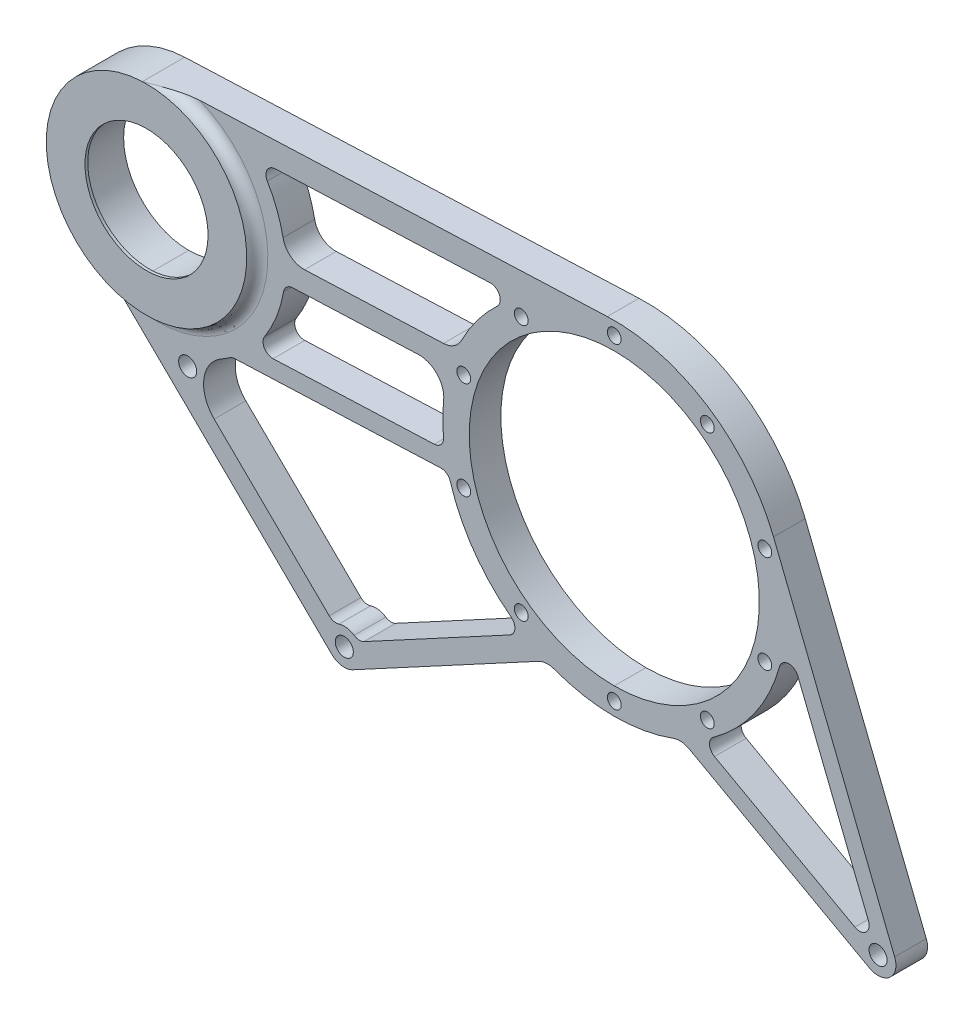
SolidWorks part; units mm, degrees
material "6061-T6 (SS)"
ref_plane "Front Plane" through (0, 0, 0) normal (0, 0, 1) x (1, 0, 0)
ref_plane "Top Plane" through (0, 0, 0) normal (0, 1, 0) x (1, 0, 0)
ref_plane "Right Plane" through (0, 0, 0) normal (1, 0, 0) x (0, 0, -1)
sketch "Sketch1" plane through (0, 0, 0) normal (0, 0, 1) x (1, 0, 0)
  line L0 (-114.3, 95.25) -> (-114.3, 107.95) construction
  line L1 (-280.8642, 163.1704) -> (-116.8043, 169.8118)
  line L2 (-304.7421, 101.1501) -> (-216.3071, 14.4521)
  line L3 (-13.0706, 21.4387) -> (-56.8054, 130.918)
  line L4 (-208.742, 13.3833) -> (-141.7118, 49.5504)
  line L5 (-22.1639, 13.4141) -> (-87.2342, 49.3665)
  circle A0 centre (-279.4, 127) radius 23.5
  circle A1 centre (-114.3, 95.25) radius 36 construction
  circle A2 centre (0, 0) radius 12.7 construction
  circle A3 centre (-228.6, 0) radius 12.7 construction
  circle A4 centre (-114.3, 107.95) radius 52.3875
  circle A5 centre (-19.05, 19.05) radius 3.2639
  circle A6 centre (-211.7995, 19.05) radius 3.2639
  circle A7 centre (-279.4, 127) radius 36.2
  arc A8 (-135.9521, 49.947) -> (-93.0137, 49.8118) centre (-114.3, 107.95) ccw
  arc A9 (-216.3071, 14.4521) -> (-208.742, 13.3833) centre (-211.7995, 19.05) ccw
  arc A10 (-22.1639, 13.4141) -> (-13.0706, 21.4387) centre (-19.05, 19.05) ccw
  arc A11 (-56.8054, 130.918) -> (-116.8043, 169.8118) centre (-114.3, 107.95) ccw
  arc A12 (-135.9521, 49.947) -> (-141.7118, 49.5504) centre (-138.3949, 43.4031) ccw
  arc A13 (-87.2342, 49.3665) -> (-93.0137, 49.8118) centre (-90.6122, 43.2526) ccw
  dimension "D5" = 72
  dimension "D6" = 47
  dimension "D7" = 25.4
  dimension "D8" = 25.4
  dimension "D11" = 104.775
  dimension "D14" = 6.5278
  dimension "D15" = 6.5278
  dimension "D16" = 25.4
  dimension "D17" = 12.7
  dimension "D18" = 123.825
  dimension "D19" = 3.175
  dimension "D20" = 6.985
  dimension "D21" = 6.985
  dimension "D1" = 114.3
  dimension "D2" = 95.25
  dimension "D3" = 279.4
  dimension "D4" = 127
  dimension "D9" = 228.6
  dimension "D10" = 12.7
  dimension "D12" = 19.05
  dimension "D13" = 19.05
extrude "Boss-Extrude1" add sketch "Sketch1" along normal blind 11.43 contours A13 L5 A10 L3 A11 L1 A7 L2 A9 L4 A12 A8 A6 A5 A4 | A7 A0 region at (-168.693, 91.0379, 0) region at (-255.035, 152.3713, 0)
sketch "Sketch2" plane through (0, 0, 11.43) normal (0, 0, 1) x (1, 0, 0)
  circle A0 centre (-279.4, 127) radius 36.2
  circle A1 centre (-279.4, 127) radius 23.5
extrude "Boss-Extrude2" add sketch "Sketch2" along normal blind 3.81
fillet "Fillet1" radius 3.81 1 edges at (-245.6173, 113.9936, 11.43)
sketch "Sketch3" plane through (0, 0, 11.43) normal (0, 0, 1) x (1, 0, 0)
  line L0 (-114.3, 107.95) -> (-114.3, 165.1) construction
  circle A0 centre (-114.3, 107.95) radius 57.15 construction
  circle A1 centre (-114.3, 165.1) radius 2.5
  circle A2 centre (-80.7081, 154.1853) radius 2.5
  circle A3 centre (-59.9471, 125.6103) radius 2.5
  circle A4 centre (-59.9471, 90.2897) radius 2.5
  circle A5 centre (-80.7081, 61.7147) radius 2.5
  circle A6 centre (-114.3, 50.8) radius 2.5
  circle A7 centre (-147.8919, 61.7147) radius 2.5
  circle A8 centre (-168.6529, 90.2897) radius 2.5
  circle A9 centre (-168.6529, 125.6103) radius 2.5
  circle A10 centre (-147.8919, 154.1853) radius 2.5
  point P25 (-114.3, 107.95)
  dimension "D1" = 114.3
  dimension "D2" = 5
  dimension "D3" = 10
extrude "5mm Holes" cut sketch "Sketch3" against normal through all
sketch "Sketch4" plane through (0, 0, 15.24) normal (0, 0, 1) x (1, 0, 0)
  circle A0 centre (-279.4, 127) radius 22.225
  circle A1 centre (-279.4, 127) radius 23.5 construction
  circle A2 centre (-279.4, 127) radius 23.5
  dimension "D1" = 44.45
extrude "Boss-Extrude3" add sketch "Sketch4" against normal blind 1
sketch "Sketch5" plane through (0, 0, 11.43) normal (0, 0, 1) x (1, 0, 0)
  line L0 (-48.0193, 91.8071) -> (-22.5033, 27.9342)
  line L1 (-13.0706, 21.4387) -> (-56.8054, 130.918) construction
  line L2 (-78.1047, 51.5771) -> (-27.4356, 23.5816)
  line L3 (-22.1639, 13.4141) -> (-87.2342, 49.3665) construction
  line L4 (-236.7455, 156.0591) -> (-159.125, 159.2013)
  line L5 (-263.8382, 163.8596) -> (-116.8043, 169.8118) construction
  line L6 (-226.1253, 129.7972) -> (-175.9845, 131.827)
  line L7 (-230.4174, 121.9972) -> (-185.1154, 123.8311)
  line L8 (-258.7869, 66.7686) -> (-217.2302, 26.028)
  line L9 (-204.6483, 24.2506) -> (-152.0143, 52.6499)
  line L10 (-292.5742, 89.2212) -> (-216.3071, 14.4521) construction
  line L11 (-208.742, 13.3833) -> (-141.7118, 49.5504) construction
  line L12 (-237.4937, 96.2899) -> (-179.3047, 98.6455)
  line L13 (-251.3498, 89.3738) -> (-177.0086, 92.3833)
  arc A0 (-175.0426, 119.9291) -> (-175.9673, 102.4457) centre (-114.3, 107.95) ccw construction
  circle A1 centre (-211.7995, 19.05) radius 6.4389 construction
  circle A2 centre (-19.05, 19.05) radius 6.4389 construction
  arc A3 (-54.6287, 91.4427) -> (-78.4387, 57.481) centre (-114.3, 107.95) cw
  arc A4 (-48.0193, 91.8071) -> (-54.6287, 91.4427) centre (-51.2626, 90.5115) ccw
  arc A5 (-27.4356, 23.5816) -> (-22.5033, 27.9342) centre (-25.7466, 26.6385) ccw
  arc A6 (-78.1047, 51.5771) -> (-78.4387, 57.481) centre (-76.4157, 54.634) cw
  arc A7 (-233.9104, 135.9413) -> (-239.6024, 150.7781) centre (-279.4, 127) ccw construction
  arc A8 (-292.5742, 89.2212) -> (-263.8382, 163.8596) centre (-279.4, 127) ccw construction
  arc A9 (-213.7352, 25.191) -> (-208.2383, 24.4145) centre (-211.7995, 19.05) cw
  arc A10 (-156.5977, 153.1613) -> (-169.499, 135.9897) centre (-114.3, 107.95) ccw
  arc A11 (-175.9093, 114.0697) -> (-175.9673, 102.4457) centre (-114.3, 107.95) ccw
  arc A12 (-173.5263, 89.9112) -> (-151.5703, 58.5123) centre (-114.3, 107.95) ccw
  arc A13 (-239.6024, 150.7781) -> (-233.9104, 135.9413) centre (-279.4, 127) cw
  arc A14 (-233.7176, 119.1025) -> (-240.5609, 101.6865) centre (-279.4, 127) cw
  arc A15 (-240.5609, 101.6865) -> (-233.7176, 119.1025) centre (-279.4, 127) ccw construction
  arc A16 (-253.1835, 88.7646) -> (-256.2406, 86.8392) centre (-279.4, 127) cw
  arc A17 (-159.125, 159.2013) -> (-156.5977, 153.1613) centre (-158.9837, 155.7117) cw
  arc A20 (-236.7455, 156.0591) -> (-239.6024, 150.7781) centre (-236.6043, 152.5695) ccw
  arc A21 (-179.3047, 98.6455) -> (-175.9673, 102.4457) centre (-179.446, 102.1352) ccw
  arc A23 (-230.4174, 121.9972) -> (-233.7176, 119.1025) centre (-230.2762, 118.5075) ccw
  arc A24 (-237.4937, 96.2899) -> (-240.5609, 101.6865) centre (-237.6349, 99.7796) cw
  arc A25 (-217.2302, 26.028) -> (-213.7352, 25.191) centre (-214.7852, 28.522) ccw
  arc A26 (-204.6483, 24.2506) -> (-208.2383, 24.4145) centre (-206.3067, 27.3242) cw
  arc A27 (-152.0143, 52.6499) -> (-151.5703, 58.5123) centre (-153.6727, 55.7236) ccw
  arc A28 (-177.0086, 92.3833) -> (-173.5263, 89.9112) centre (-176.8673, 88.8936) cw
  arc A29 (-251.3498, 89.3738) -> (-253.1835, 88.7646) centre (-251.2085, 85.8842) ccw
  arc A31 (-173.5263, 89.9112) -> (-170.4887, 133.9499) centre (-114.3, 107.95) ccw construction
  arc A32 (-273.3418, 81.0375) -> (-253.1835, 88.7646) centre (-279.4, 127) ccw construction
  arc A33 (-258.7869, 66.7686) -> (-256.2406, 86.8392) centre (-249.8962, 75.8374) cw
  arc A34 (-169.499, 135.9897) -> (-175.9845, 131.827) centre (-176.2928, 139.4407) cw
  arc A35 (-233.9104, 135.9413) -> (-226.1253, 129.7972) centre (-226.4335, 137.411) ccw
  arc A36 (-185.1154, 123.8311) -> (-175.9093, 114.0697) centre (-184.7558, 114.9484) cw
  point P17 (-52.5701, 103.1988)
  point P23 (-83.2204, 54.4036)
  point P51 (-148.3837, 159.6362)
  point P54 (-171.3442, 132.0148)
  point P60 (-243.0732, 155.8029)
  point P63 (-175.5324, 98.7982)
  point P66 (-174.02, 124.2803)
  point P75 (-215.4925, 24.3245)
  point P78 (-206.7898, 23.0951)
  point P81 (-146.981, 55.3657)
  point P84 (-174.2524, 92.4948)
  point P90 (-273.3418, 81.0375)
  dimension "D1" = 123.825
  dimension "D2" = 12.8778
  dimension "D5" = 3.4925
  dimension "D6" = 6.35
  dimension "D14" = 3.4925
  dimension "D15" = 12.7
  dimension "D16" = 7.62
  dimension "D17" = 7.62
  dimension "D18" = 8.89
  dimension "D3" = 6.35
  dimension "D4" = 6.35
  dimension "D7" = 8.89
  dimension "D8" = 7.62
  dimension "D9" = 7.62
  dimension "D10" = 7.62
  dimension "D11" = 6.35
  dimension "D12" = 25.4
  dimension "D13" = 26.67
extrude "Cut-Extrude2" cut sketch "Sketch5" against normal through all both and the other way through all
ref_axis "Axis2" through (-279.4, 127, 14.24) along (0, 0, -1)
ref_axis "Axis1" through (-114.3, 107.95, 11.43) along (0, 0, -1)
ref_plane "Plane1" through (-114.3, 0, 0) normal (1, 0, 0) x (0, 0, -1)
ref_plane "Plane2" through (-279.4, 0, 0) normal (1, 0, 0) x (0, 0, -1)
ref_plane "Plane3" through (0, 0, 5.715) normal (0, 0, -1) x (-1, 0, 0)
ref_plane "Plane4" through (0, 0, 7.12) normal (0, 0, -1) x (-1, 0, 0)
split line "Split Line1"
split line "Split Line2"
sketch "Sketch6" plane through (0, 0, 5.715) normal (0, 0, -1) x (-1, 0, 0)
  circle A1 centre (114.3, 107.95) radius 52.3875 construction
sketch "Sketch7" plane through (0, 0, 7.12) normal (0, 0, -1) x (-1, 0, 0)
  circle A0 centre (279.4, 127) radius 23.5
sketch "Sketch8" plane through (0, 0, 11.43) normal (0, 0, 1) x (1, 0, 0)
  circle A0 centre (-268.3542, 78.4783) radius 3.2639
extrude "Cut-Extrude3" cut sketch "Sketch8" against normal through all both and the other way through all
ref_point "Puck Center"
ref_point "Bearing Center"
sketch "Sketch9" plane through (0, 0, 0) normal (0, 0, 1) x (1, 0, 0)
  point P0 (-48.5383, 56.2255)
  point P1 (-206.2691, 109.9745)
  point P2 (-217.3203, 145.1375)
  point P3 (-185.1714, 145.1375)
  point P4 (-230.3808, 72.3)
  point P5 (-206.2691, 46.179)
  point P6 (-185.1714, 69.286)
  point P7 (-113.8939, 82.1055)
  point P8 (-149.5374, 107.95)
  point P9 (-114.3, 142.6648)
  point P10 (-77.5583, 107.95)
  point P11 (-279.4, 138.8583)
  point P12 (-279.4, 118.0951)
